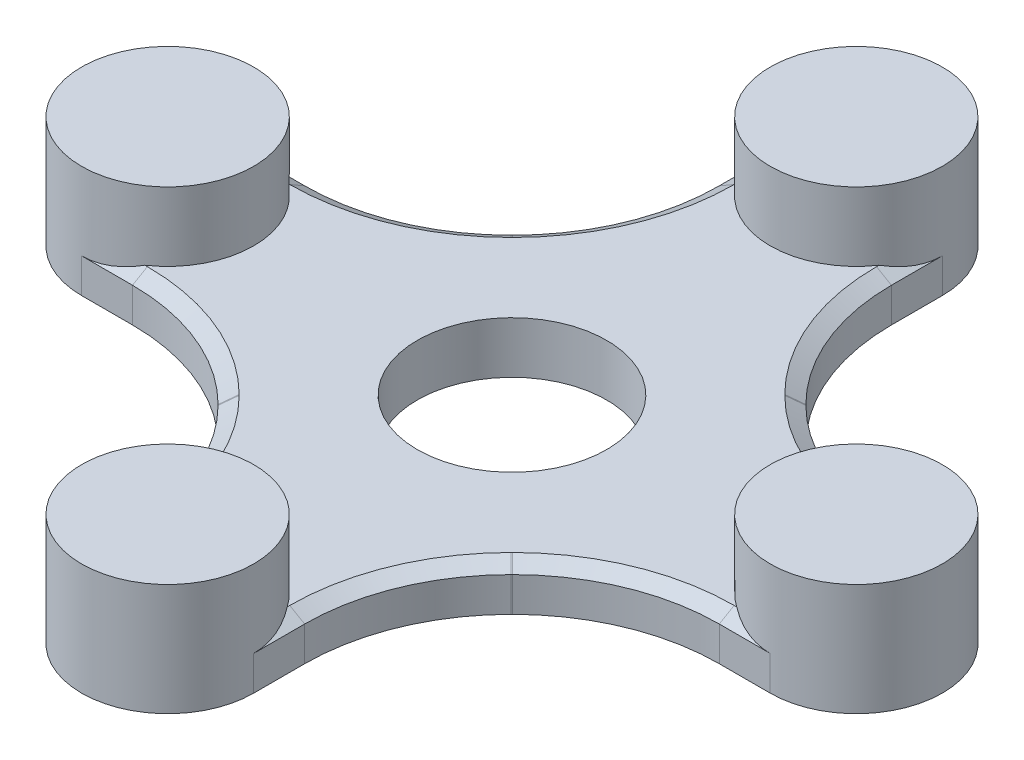
SolidWorks part; units mm, degrees
material "ABS"
ref_plane "Front Plane" through (0, 0, 0) normal (0, 0, 1) x (1, 0, 0)
ref_plane "Top Plane" through (0, 0, 0) normal (0, 1, 0) x (1, 0, 0)
ref_plane "Right Plane" through (0, 0, 0) normal (1, 0, 0) x (0, 0, -1)
sketch "Sketch2" plane through (0, 0, 0) normal (0, 1, 0) x (1, 0, 0)
  line L0 (-5, 25) -> (-5, 12.0711)
  line L1 (-25, -25) -> (25, -25) construction
  line L2 (-25, -25) -> (-25, 25) construction
  line L3 (-25, 25) -> (25, 25) construction
  line L4 (25, -25) -> (25, 25) construction
  line L5 (-25, -25) -> (25, 25) construction
  line L6 (-25, 25) -> (25, -25) construction
  line L7 (-5, 12.0711) -> (-12.0711, 5)
  line L8 (-12.0711, 5) -> (-25, 5)
  line L9 (-25, 5) -> (-25, -5)
  line L10 (-25, -5) -> (-12.0711, -5)
  line L11 (-12.0711, -5) -> (-5, -12.0711)
  line L12 (-5, -12.0711) -> (-5, -25)
  line L13 (-5, -25) -> (5, -25)
  line L14 (5, -25) -> (5, -12.0711)
  line L15 (5, -12.0711) -> (12.0711, -5)
  line L16 (12.0711, -5) -> (25, -5)
  line L17 (25, -5) -> (25, 5)
  line L18 (25, 5) -> (12.0711, 5)
  line L19 (12.0711, 5) -> (5, 12.0711)
  line L20 (5, 12.0711) -> (5, 25)
  line L21 (5, 25) -> (-5, 25)
  point P0 (0, 0)
  point P19 (0, 25)
  point P23 (0, -25)
  point P24 (-25, 0)
  point P25 (25, 0)
  dimension "D1" = 10
  dimension "D2" = 10
  dimension "D3" = 50
extrude "Boss-Extrude2" add sketch "Sketch2" along normal blind 3
sketch "Sketch3" plane through (0, 3, 0) normal (0, 1, 0) x (1, 0, 0)
  line L0 (0, 20) -> (0, -20) construction
  line L1 (20, 0) -> (-20, 0) construction
  line L2 (-12.0711, 5) -> (-25, 5) construction
  line L4 (-55, 0) -> (55, 0) construction
  line L5 (-25, 5) -> (-25, -5) construction
  circle A0 centre (-20, 0) radius 5
  circle A1 centre (0, 20) radius 5
  circle A2 centre (20, 0) radius 5
  circle A3 centre (0, -20) radius 5
  point P8 (0, 0)
  point P9 (0, 0)
  point P15 (-16.6262, 0)
extrude "Boss-Extrude3" add sketch "Sketch3" along normal blind 4
fillet "Fillet2" radius 12 8 edges at (-12.0711, 1.5, -5) (-5, 1.5, -12.0711) (5, 1.5, -12.0711) (12.0711, 1.5, -5) (12.0711, 1.5, 5) (5, 1.5, 12.0711) (-12.0711, 1.5, 5) (-5, 1.5, 12.0711)
sketch "Sketch4" plane through (0, 3, 0) normal (0, 1, 0) x (1, 0, 0)
  line L24 (-5, -25) -> (0, -25) construction
  line L25 (-5, -20) -> (-5, -25) construction
  line L26 (5, -25) -> (5, -20) construction
  line L27 (0, -25) -> (5, -25) construction
  line L28 (25, -5) -> (25, 0) construction
  line L29 (20, -5) -> (25, -5) construction
  line L30 (25, 5) -> (20, 5) construction
  line L31 (25, 0) -> (25, 5) construction
  line L32 (5, 25) -> (0, 25) construction
  line L33 (5, 20) -> (5, 25) construction
  line L34 (-5, 25) -> (-5, 20) construction
  line L35 (0, 25) -> (-5, 25) construction
  line L36 (-25, 0) -> (-25, -5) construction
  line L37 (-25, -5) -> (-20, -5) construction
  line L38 (-20, 5) -> (-25, 5) construction
  line L39 (-25, 5) -> (-25, 0) construction
  line L40 (-5, -25) -> (0, -25)
  line L41 (-5, -20) -> (-5, -25)
  line L42 (5, -25) -> (5, -20)
  line L43 (0, -25) -> (5, -25)
  line L44 (25, -5) -> (25, 0)
  line L45 (20, -5) -> (25, -5)
  line L46 (25, 5) -> (20, 5)
  line L47 (25, 0) -> (25, 5)
  line L48 (5, 25) -> (0, 25)
  line L49 (5, 20) -> (5, 25)
  line L50 (-5, 25) -> (-5, 20)
  line L51 (0, 25) -> (-5, 25)
  line L52 (-25, 0) -> (-25, -5)
  line L53 (-25, -5) -> (-20, -5)
  line L54 (-20, 5) -> (-25, 5)
  line L55 (-25, 5) -> (-25, 0)
  arc A8 (-5, -20) -> (0, -25) centre (0, -20) ccw construction
  arc A9 (0, -25) -> (5, -20) centre (0, -20) ccw construction
  arc A10 (20, -5) -> (25, 0) centre (20, 0) ccw construction
  arc A11 (25, 0) -> (20, 5) centre (20, 0) ccw construction
  arc A12 (5, 20) -> (0, 25) centre (0, 20) ccw construction
  arc A13 (0, 25) -> (-5, 20) centre (0, 20) ccw construction
  arc A14 (-25, 0) -> (-20, -5) centre (-20, 0) ccw construction
  arc A15 (-20, 5) -> (-25, 0) centre (-20, 0) ccw construction
  arc A16 (-5, -20) -> (0, -25) centre (0, -20) ccw
  arc A17 (0, -25) -> (5, -20) centre (0, -20) ccw
  arc A18 (20, -5) -> (25, 0) centre (20, 0) ccw
  arc A19 (25, 0) -> (20, 5) centre (20, 0) ccw
  arc A20 (5, 20) -> (0, 25) centre (0, 20) ccw
  arc A21 (0, 25) -> (-5, 20) centre (0, 20) ccw
  arc A22 (-25, 0) -> (-20, -5) centre (-20, 0) ccw
  arc A23 (-20, 5) -> (-25, 0) centre (-20, 0) ccw
  circle A24 centre (0, 0) radius 5.5
  dimension "D1" = 11
extrude "Cut-Extrude1" cut sketch "Sketch4" against normal up to next contours A22 L52 L53 | A23 L54 L55 | A21 L51 L50 | A20 L49 L48 | A19 L47 L46 | A18 L45 L44 | A17 L43 L42 | A16 L41 L40 | A24 region at (-3.8832, 3, 23.8832) region at (3.8832, 3, 23.8832) region at (23.8832, 3, 3.8832) region at (23.8832, 3, -3.8832) region at (3.8832, 3, -23.8832) region at (-3.8832, 3, -23.8832) region at (-23.8832, 3, 3.8832) region at (-23.8832, 3, -3.8832)
chamfer "Chamfer1" distance 0.5 angle 60 44 edges at (5, 3, -18.5208) (5.9134, 3, -12.4494) (18.5208, 3, -5) (8.5355, 3, -8.5355) (12.4494, 3, -5.9134) (-18.5208, 3, -5) (-12.4494, 3, -5.9134) (-5, 3, -18.5208) (-8.5355, 3, -8.5355) (-5.9134, 3, -12.4494) (-5, 3, 18.5208) (-5.9134, 3, 12.4494) (-18.5208, 3, 5) (-8.5355, 3, 8.5355) (-12.4494, 3, 5.9134) (-12.4494, 0, -5.9134) (-8.5355, 0, -8.5355) (-18.5208, 0, -5) (-5.9134, 0, -12.4494) (-25, 0, 0) (-5, 0, -18.5208) (-18.5208, 0, 5) (0, 0, -25) (-12.4494, 0, 5.9134) (5, 0, -18.5208) (-8.5355, 0, 8.5355) (5.9134, 0, -12.4494) (-5.9134, 0, 12.4494) (8.5355, 0, -8.5355) (-5, 0, 18.5208) (12.4494, 0, -5.9134) (0, 0, 25) (18.5208, 0, -5) (5, 0, 18.5208) (25, 0, 0) (5.9134, 0, 12.4494) (18.5208, 0, 5) (8.5355, 0, 8.5355) (12.4494, 0, 5.9134) (5, 3, 18.5208) (5.9134, 3, 12.4494) (8.5355, 3, 8.5355) (18.5208, 3, 5) (12.4494, 3, 5.9134) first distance on face at (5, 1.5, -18.5208) first distance on face at (6.3354, 1.5, -12.6242) first distance on face at (18.5208, 1.5, -5) first distance on face at (8.5355, 1.5, -8.5355) first distance on face at (12.6242, 1.5, -6.3354) first distance on face at (-18.5208, 1.5, -5) first distance on face at (-12.6242, 1.5, -6.3354) first distance on face at (-5, 1.5, -18.5208) first distance on face at (-8.5355, 1.5, -8.5355) first distance on face at (-6.3354, 1.5, -12.6242) first distance on face at (-5, 1.5, 18.5208) first distance on face at (-6.3354, 1.5, 12.6242) first distance on face at (-18.5208, 1.5, 5) first distance on face at (-8.5355, 1.5, 8.5355) first distance on face at (-12.6242, 1.5, 6.3354) first distance on face at (-20, 7, 5) first distance on face at (0, 7, -15) first distance on face at (0, 7, 25) first distance on face at (5, 1.5, 18.5208) first distance on face at (20, 7, 5) first distance on face at (6.3354, 1.5, 12.6242) first distance on face at (18.5208, 1.5, 5) first distance on face at (8.5355, 1.5, 8.5355) first distance on face at (12.6242, 1.5, 6.3354)
